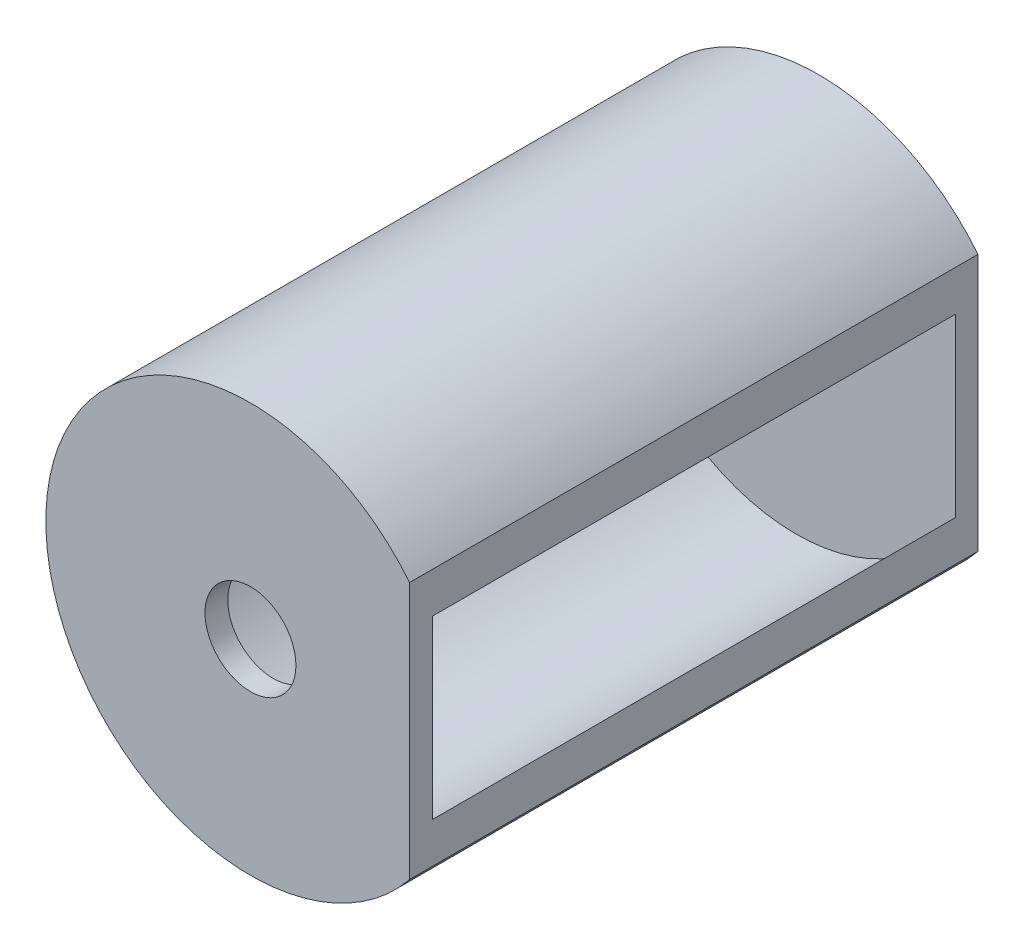
SolidWorks part; units mm, degrees
material "Malleable Cast Iron"
ref_plane "Front Plane" through (0, 0, 0) normal (0, 0, 1) x (1, 0, 0)
ref_plane "Top Plane" through (0, 0, 0) normal (0, 1, 0) x (1, 0, 0)
ref_plane "Right Plane" through (0, 0, 0) normal (1, 0, 0) x (0, 0, -1)
sketch "Sketch1" plane through (0, 0, 0) normal (0, 0, 1) x (1, 0, 0)
  circle A0 centre (0, 0) radius 18
  circle A1 centre (0, 0) radius 16
  dimension "D1" = 36
  dimension "D2" = 2
extrude "Boss-Extrude1" add sketch "Sketch1" along normal blind 50
sketch "Sketch3" plane through (0, 0, 0) normal (0, 0, -1) x (-1, 0, 0)
  circle A1 centre (0, 0) radius 18
extrude "Boss-Extrude2" add sketch "Sketch3" against normal blind 2
extrude "Boss-Extrude3" add sketch "Sketch3<2>" along normal blind 2 from surface starting at face at (18, 0, 50)
sketch "Sketch3<2>" plane through (0, 0, 0) normal (0, 0, -1) x (-1, 0, 0) same geometry as "Sketch3"
sketch "Sketch2" plane through (0, 0, 0) normal (1, 0, 0) x (0, 0, -1)
  line L0 (0, 18) -> (-50, 18) construction
  line L1 (0, 18) -> (-50, 18)
  line L2 (0, 18) -> (0, -18)
  line L3 (0, -18) -> (-50, -18)
  line L4 (-50, 18) -> (-50, -18)
  line L5 (-50, -18) -> (0, -18) construction
  line L6 (-50, 18) -> (-50, -18) construction
  dimension "D1" = 50
  dimension "D2" = 0
extrude "Cut-Extrude1" cut sketch "Sketch2" along normal blind 150 from offset 14
sketch "Sketch4" plane through (0, 0, 50) normal (0, 0, 1) x (1, 0, 0)
  circle A0 centre (0, 0) radius 4
  dimension "D1" = 8
extrude "Cut-Extrude2" cut sketch "Sketch4" against normal through all both and the other way through all
